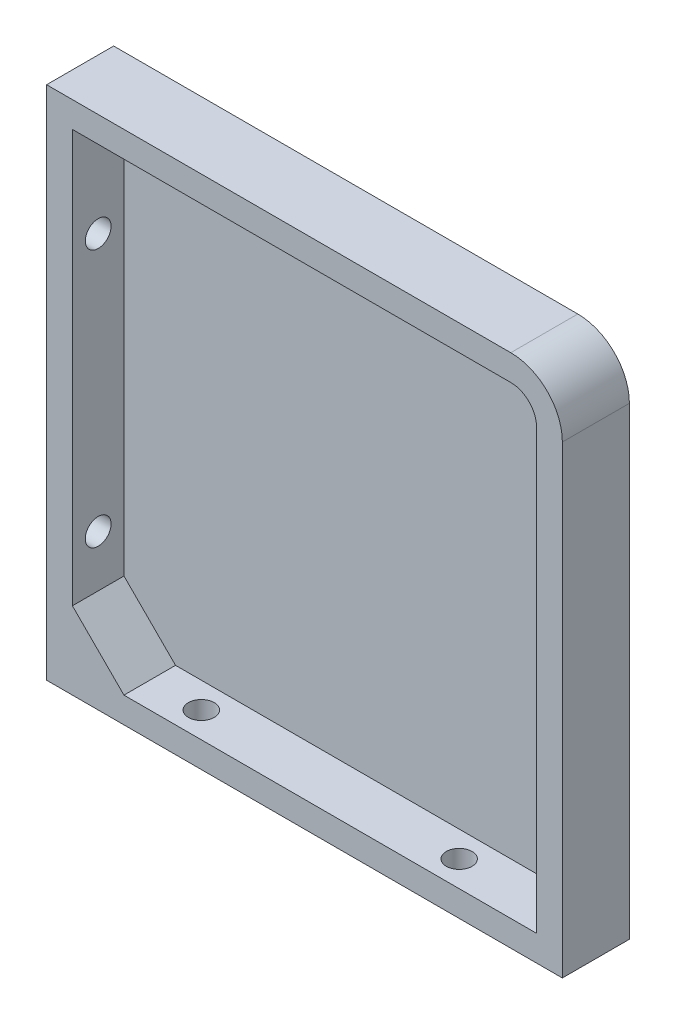
SolidWorks part; units mm, degrees
ref_plane "Plan de face" through (0, 0, 0) normal (0, 0, 1) x (1, 0, 0)
ref_plane "Plan de dessus" through (0, 0, 0) normal (0, 1, 0) x (1, 0, 0)
ref_plane "Plan de droite" through (0, 0, 0) normal (1, 0, 0) x (0, 0, -1)
sketch "Esquisse1" plane through (0, 0, 0) normal (0, 0, 1) x (1, 0, 0)
  line L1 (-45.8816, 33.7284) -> (44.1184, 33.7284)
  line L2 (-45.8816, 33.7284) -> (-45.8816, -66.2716)
  line L3 (-45.8816, -66.2716) -> (54.1184, -66.2716)
  line L4 (54.1184, 23.7284) -> (54.1184, -66.2716)
  arc A0 (44.1184, 33.7284) -> (54.1184, 23.7284) centre (44.1184, 23.7284) cw
  point P6 (54.1184, 33.7284)
  dimension "D3" = 10
  dimension "D1" = 100
  dimension "D2" = 100
extrude "Boss.-Extru.1" add sketch "Esquisse1" along normal blind 13
shell "Coque1" thickness 5 removed face at (12.5326, -7.8573, 13)
sketch "Esquisse2" plane through (-45.8816, 0, 0) normal (-1, 0, 0) x (0, 0, 1)
  line L0 (13, 33.7284) -> (13, -66.2716) construction
  line L1 (13, 33.7284) -> (0, 33.7284) construction
  line L2 (13, -66.2716) -> (0, -66.2716) construction
  circle A0 centre (8, 8.7284) radius 2.5
  circle A1 centre (8, -41.2716) radius 2.5
  dimension "D1" = 5
  dimension "D2" = 5
  dimension "D3" = 5
  dimension "D4" = 5
  dimension "D5" = 25
  dimension "D6" = 25
extrude "Enlèv. mat.-Extru.1" cut sketch "Esquisse2" against normal up to surface (5 mm away) contours A1 | A0 region at (-45.8816, -41.2716, 8) up to face at (-40.8816, -16.2716, 8)
sketch "Esquisse3" plane through (0, -66.2716, 0) normal (0, -1, 0) x (1, 0, 0)
  line L0 (-45.8816, 13) -> (54.1184, 13) construction
  line L2 (54.1184, 13) -> (54.1184, 0) construction
  line L3 (-45.8816, 13) -> (-45.8816, 0) construction
  circle A0 centre (-20.8816, 8) radius 2.5
  circle A1 centre (29.1184, 8) radius 2.5
  dimension "D1" = 5
  dimension "D2" = 5
  dimension "D3" = 5
  dimension "D4" = 5
  dimension "D5" = 25
  dimension "D6" = 25
extrude "Enlèv. mat.-Extru.2" cut sketch "Esquisse3" against normal up to surface (5 mm away) up to face at (4.1184, -61.2716, 8)
sketch "Esquisse4" plane through (0, 0, 3) normal (0, 0, 1) x (1, 0, 0)
  line L0 (-40.8816, -51.2716) -> (-30.8816, -61.2716)
  line L1 (-40.8816, 28.7284) -> (-40.8816, -61.2716) construction
  line L2 (-40.8816, -61.2716) -> (49.1184, -61.2716) construction
  line L3 (-30.8816, -61.2716) -> (-40.8816, -61.2716)
  line L4 (-40.8816, -61.2716) -> (-40.8816, -51.2716)
  dimension "D1" = 10
  dimension "D2" = 10
extrude "Boss.-Extru.2" add sketch "Esquisse4" along normal up to surface (10 mm away) up to face at (12.5326, -7.8573, 13)
